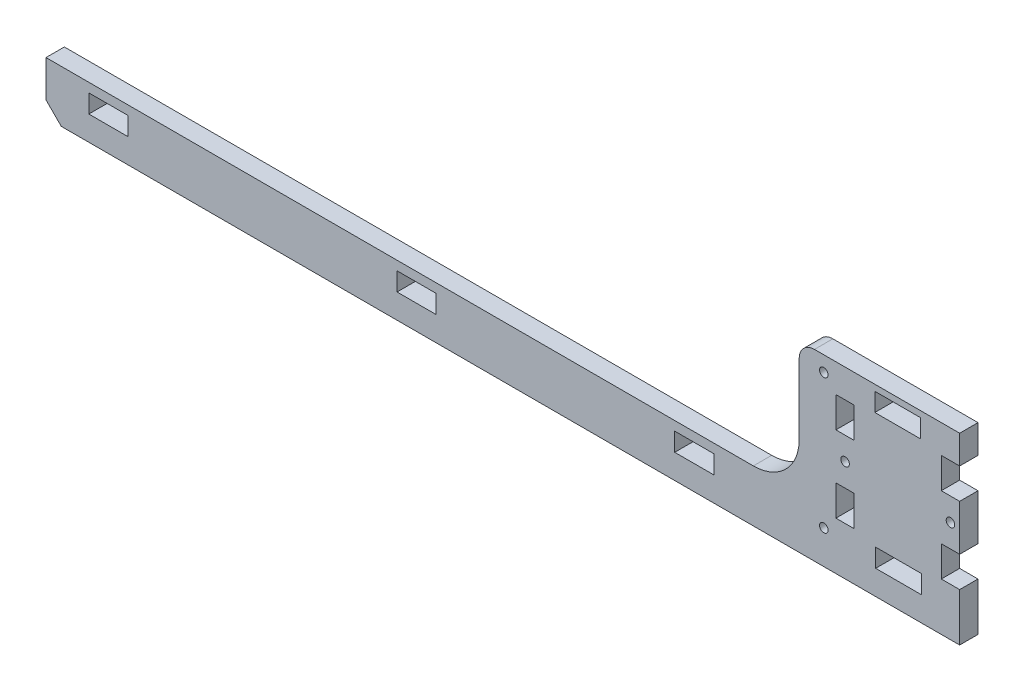
SolidWorks part; units mm, degrees
ref_plane "Front" through (0, 0, 0) normal (0, 0, 1) x (1, 0, 0)
ref_plane "Top" through (0, 0, 0) normal (0, 1, 0) x (1, 0, 0)
ref_plane "Right" through (0, 0, 0) normal (1, 0, 0) x (0, 0, -1)
sketch "Эскиз1" plane through (0, 0, 0) normal (0, 0, 1) x (1, 0, 0)
  line L46 (96.9208, 2) -> (96.9208, 25)
  line L54 (101.9208, 30) -> (149.3892, 30)
  line L55 (149.3892, 30) -> (149.3892, 20.7093)
  line L56 (149.3892, -30) -> (-144.3892, -30)
  line L57 (-144.3892, -30) -> (-149.3892, -25)
  line L58 (-149.3892, -25) -> (-149.3892, -13)
  line L59 (81.9208, -13) -> (-149.3892, -13)
  line L60 (-135.3886, -16) -> (-122.5886, -16)
  line L61 (-135.3886, -16) -> (-135.3886, -22)
  line L62 (-135.3886, -22) -> (-122.5886, -22)
  line L63 (-122.5886, -16) -> (-122.5886, -22)
  line L64 (-34.5886, -16) -> (-21.7886, -16)
  line L65 (-34.5886, -16) -> (-34.5886, -22)
  line L66 (-34.5886, -22) -> (-21.7886, -22)
  line L67 (-21.7886, -16) -> (-21.7886, -22)
  line L68 (56.2114, -16) -> (69.0114, -16)
  line L69 (56.2114, -16) -> (56.2114, -22)
  line L70 (56.2114, -22) -> (69.0114, -22)
  line L71 (69.0114, -16) -> (69.0114, -22)
  line L72 (121.9208, -16) -> (136.9208, -16)
  line L73 (121.9208, -16) -> (121.9208, -22)
  line L74 (121.9208, -22) -> (136.9208, -22)
  line L75 (136.9208, -16) -> (136.9208, -22)
  line L76 (143.3892, 20.7093) -> (149.3892, 20.7093)
  line L77 (143.3892, 20.7093) -> (143.3892, 10.7093)
  line L78 (143.3892, 10.7093) -> (149.3892, 10.7093)
  line L80 (143.3892, -4.2907) -> (149.3892, -4.2907)
  line L81 (143.3892, -4.2907) -> (143.3892, -14.2907)
  line L82 (143.3892, -14.2907) -> (149.3892, -14.2907)
  line L84 (108.9208, 20.7093) -> (114.9208, 20.7093)
  line L85 (108.9208, 20.7093) -> (108.9208, 10.7093)
  line L86 (108.9208, 10.7093) -> (114.9208, 10.7093)
  line L87 (114.9208, 20.7093) -> (114.9208, 10.7093)
  line L88 (108.9208, -14.2907) -> (114.9208, -14.2907)
  line L89 (108.9208, -14.2907) -> (108.9208, -4.2907)
  line L90 (108.9208, -4.2907) -> (114.9208, -4.2907)
  line L91 (114.9208, -14.2907) -> (114.9208, -4.2907)
  line L92 (121.6558, 28) -> (136.6558, 28)
  line L93 (121.6558, 28) -> (121.6558, 22)
  line L94 (121.6558, 22) -> (136.6558, 22)
  line L95 (136.6558, 28) -> (136.6558, 22)
  line L105 (149.3892, 10.7093) -> (149.3892, -4.2907)
  line L106 (149.3892, -14.2907) -> (149.3892, -30)
  line L107 (111.9208, 10.7093) -> (111.9208, -4.2907) construction
  line L108 (146.3892, 10.7093) -> (146.3892, -4.2907) construction
  line L109 (108.9208, 3.2093) -> (149.3892, 3.2405) construction
  arc A6 (96.9208, 2) -> (81.9208, -13) centre (81.9208, 2) cw
  arc A7 (96.9208, 25) -> (101.9208, 30) centre (101.9208, 25) cw
  circle A8 centre (104.9708, -19) radius 1.4
  circle A9 centre (104.9708, 25) radius 1.4
  circle A10 centre (111.9208, 3.2093) radius 1.4
  circle A11 centre (146.3892, 3.2093) radius 1.4
  dimension "D1" = 2.8
  dimension "D2" = 2.8
extrude "Бобышка-Вытянуть1" add sketch "Эскиз1" along normal blind 6
